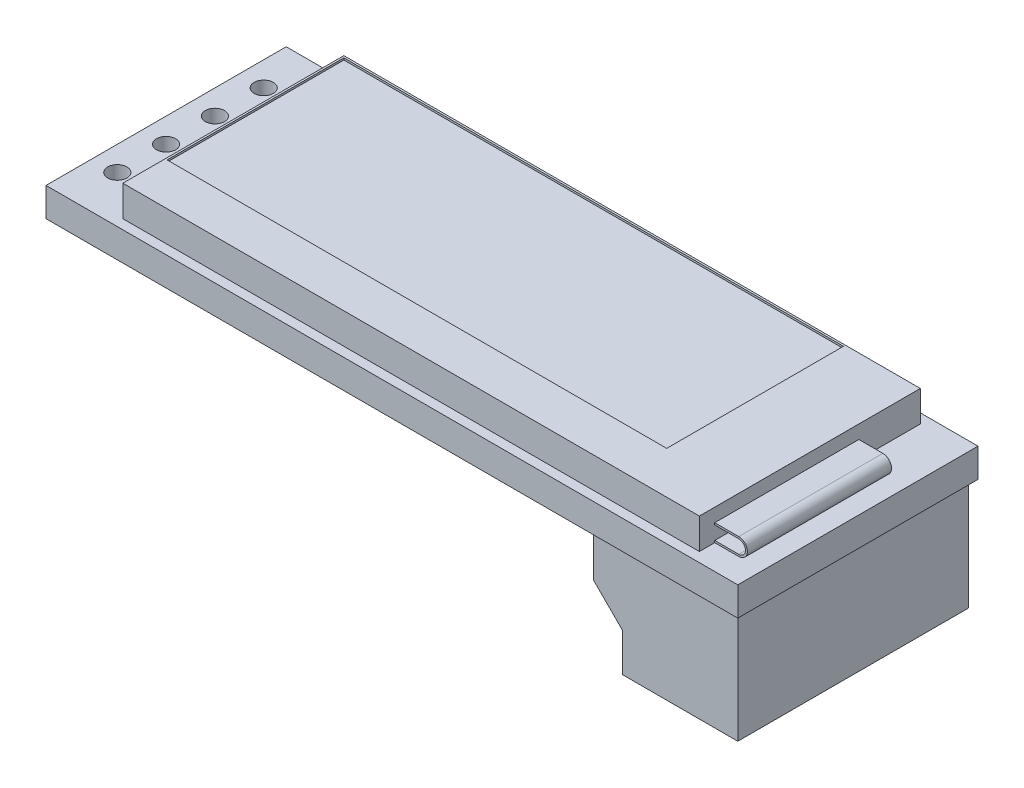
SolidWorks part; units mm, degrees
ref_plane "Front Plane" through (0, 0, 0) normal (0, 0, 1) x (1, 0, 0)
ref_plane "Top Plane" through (0, 0, 0) normal (0, 1, 0) x (1, 0, 0)
ref_plane "Right Plane" through (0, 0, 0) normal (1, 0, 0) x (0, 0, -1)
sketch "Sketch1" plane through (0, 0, 0) normal (0, 1, 0) x (1, 0, 0)
  line L1 (18, 6.25) -> (-18, 6.25)
  line L2 (18, 6.25) -> (18, -6.25)
  line L3 (18, -6.25) -> (-18, -6.25)
  line L4 (-18, 6.25) -> (-18, -6.25)
  line L5 (18, 6.25) -> (-18, -6.25) construction
  line L6 (18, -6.25) -> (-18, 6.25) construction
  point P0 (0, 0)
  dimension "D1" = 36
  dimension "D2" = 12.5
extrude "Boss-Extrude1" add sketch "Sketch1" along normal blind 1.5
sketch "Sketch2" plane through (0, 1.5, 0) normal (0, 1, 0) x (1, 0, 0)
  line L0 (-18, 6.25) -> (-18, -6.25) construction
  line L1 (-18, -6.25) -> (18, -6.25) construction
  circle A0 centre (-16.73, -3.81) radius 0.5
  dimension "D2" = 2.44
  dimension "D3" = 1
  dimension "D1" = 1.27
extrude "Cut-Extrude1" cut sketch "Sketch2" against normal through all
pattern_linear "LPattern1" count 4 spacing 2.54 along (0, 0, -1) of "Cut-Extrude1"
sketch "Sketch3" plane through (0, 0, 0) normal (0, -1, 0) x (1, 0, 0)
  line L0 (18, 6.25) -> (18, -6.25) construction
  line L1 (17.75, -6) -> (10.25, -6)
  line L2 (17.75, -6) -> (17.75, 6)
  line L3 (17.75, 6) -> (10.25, 6)
  line L4 (10.25, -6) -> (10.25, 6)
  line L5 (17.75, -6) -> (10.25, 6) construction
  line L6 (17.75, 6) -> (10.25, -6) construction
  line L7 (18, -6.25) -> (-18, -6.25) construction
  point P0 (14, 0)
  point P9 (0, 0)
  dimension "D1" = 0.25
  dimension "D2" = 7.5
  dimension "D3" = 0.25
extrude "Boss-Extrude2" add sketch "Sketch3" along normal blind 5.8
sketch "Sketch4" plane through (0, 0, 6) normal (0, 0, 1) x (1, 0, 0)
  line L1 (10.25, -5.8) -> (11.75, -5.8)
  line L2 (10.25, -5.8) -> (10.25, -3.8)
  line L3 (10.25, -3.8) -> (11.75, -3.8)
  line L4 (11.75, -5.8) -> (11.75, -3.8)
  dimension "D1" = 1.5
  dimension "D2" = 2
extrude "Cut-Extrude2" cut sketch "Sketch4" against normal through all
chamfer "Chamfer1" distance 1.5 angle 45 1 edges at (10.25, -3.8, 0)
sketch "Sketch5" plane through (0, 1.5, 0) normal (0, 1, 0) x (1, 0, 0)
  line L0 (-18, 6.25) -> (-18, -6.25) construction
  line L1 (15.5, 5.75) -> (-14.5, 5.75)
  line L2 (15.5, 5.75) -> (15.5, -5.75)
  line L3 (15.5, -5.75) -> (-14.5, -5.75)
  line L4 (-14.5, 5.75) -> (-14.5, -5.75)
  line L5 (15.5, 5.75) -> (-14.5, -5.75) construction
  line L6 (15.5, -5.75) -> (-14.5, 5.75) construction
  point P0 (0.5, 0)
  point P5 (3.3322, 0)
  dimension "D1" = 30
  dimension "D2" = 11.5
  dimension "D3" = 3.5
extrude "Boss-Extrude3" add sketch "Sketch5" along normal blind 1.6
sketch "Sketch6" plane through (0, 0, 5.75) normal (0, 0, 1) x (1, 0, 0)
  line L0 (15.5, 1.5) -> (16.75, 1.5)
  line L1 (-18, 1.5) -> (18, 1.5) construction
  line L2 (16.75, 2.4) -> (15.5, 2.4)
  line L3 (15.5, 3.1) -> (15.5, 1.5) construction
  line L4 (18, 1.5) -> (18, 0) construction
  line L5 (-14.5, 3.1) -> (15.5, 3.1) construction
  arc A0 (16.75, 1.5) -> (16.75, 2.4) centre (16.75, 1.95) ccw
  dimension "D1" = 0.8
  dimension "D2" = 0.7
extrude "Extrude-Thin1" add sketch "Sketch6" against normal blind 7.5 from offset 0.8 thin offset against normal yes thin type one direction reverse wall 0.1
sketch "Sketch7" plane through (0, 3.1, 0) normal (0, 1, 0) x (1, 0, 0)
  line L0 (-14.5, -5.75) -> (15.5, -5.75) construction
  line L1 (11.6, -3.55) -> (-14.4, -3.55)
  line L2 (11.6, -3.55) -> (11.6, 5.65)
  line L3 (11.6, 5.65) -> (-14.4, 5.65)
  line L4 (-14.4, -3.55) -> (-14.4, 5.65)
  line L5 (11.6, -3.55) -> (-14.4, 5.65) construction
  line L6 (11.6, 5.65) -> (-14.4, -3.55) construction
  line L7 (-14.5, 5.75) -> (-14.5, -5.75) construction
  line L8 (15.5, 5.75) -> (-14.5, 5.75) construction
  point P0 (-1.4, 1.05)
  dimension "D1" = 2.2
  dimension "D2" = 0.1
  dimension "D3" = 0.1
  dimension "D4" = 26
extrude "Cut-Extrude3" cut sketch "Sketch7" against normal blind 0.1
equation "\"D3@Sketch3\"=\"D1@Sketch3\""
equation "\"D3@Sketch7\"=\"D2@Sketch7\""
